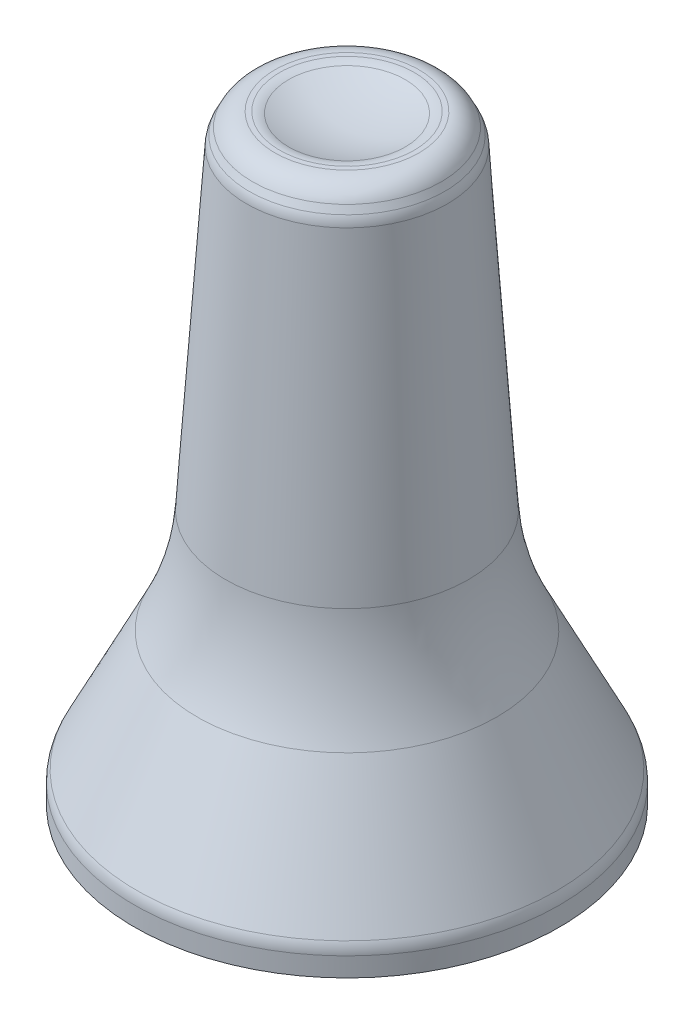
SolidWorks part; units mm, degrees
ref_plane "Front Plane" through (0, 0, 0) normal (0, 0, 1) x (1, 0, 0)
ref_plane "Top Plane" through (0, 0, 0) normal (0, 1, 0) x (1, 0, 0)
ref_plane "Right Plane" through (0, 0, 0) normal (1, 0, 0) x (0, 0, -1)
sketch "Sketch1" plane through (0, 0, 0) normal (0, 0, 1) x (1, 0, 0)
  line L0 (0, 0) -> (8.5, 0)
  line L1 (8.5, 0) -> (8.5, 1)
  line L2 (8.5, 1) -> (5, 8)
  line L3 (5, 8) -> (4, 23)
  line L4 (4, 23) -> (3.5, 24)
  line L5 (3.5, 24) -> (2.5, 24)
  line L6 (2.5, 24) -> (1.3, 23.5) construction
  line L7 (0, 23.5) -> (0, 0) construction
  line L8 (0, 0) -> (0, 23.5)
  line L9 (1.3, 23.5) -> (0, 23.5) construction
  spline S0 degree 2 poles (2.5, 24) (1.3, 23.5) (0, 23.5) knots 0 0 0 1 1 1
  dimension "D1" = 24
  dimension "D2" = 4
  dimension "D3" = 1
  dimension "D4" = 8
  dimension "D5" = 1
  dimension "D6" = 0.5
  dimension "D7" = 0.5
  dimension "D8" = 1
  dimension "D9" = 8.5
  dimension "D10" = 5
revolve "Revolve1" add sketch "Sketch1" angle 360 about L7
fillet "Fillet1" radius 11 1 edges at (-5, 8, 0)
fillet "Fillet2" radius 1 4 edges at (-2.5, 24, 0) (-3.5, 24, 0) (-4, 23, 0) (-8.5, 1, 0)
sketch "Sketch3" plane through (0, 0, 0) normal (0, 0, 1) x (1, 0, 0)
  line L0 (0, 0) -> (3.875, 0)
  line L1 (-8.5, 0) -> (8.5, 0) construction
  line L2 (3.875, 0) -> (3.875, 6.5)
  line L3 (3.875, 6.5) -> (3.05, 7.325)
  line L4 (3.05, 7.325) -> (3.05, 17.75)
  line L5 (3.05, 17.75) -> (0, 17.75)
  line L6 (0, 17.75) -> (0, 0)
  dimension "D1" = 17.75
  dimension "D2" = 3.875
  dimension "D3" = 45
  dimension "D4" = 3.05
  dimension "D5" = 6.5
revolve "Cut-Revolve1" cut sketch "Sketch3" angle 360 about L6
ref_plane "Plane1" through (0, 7.325, 0) normal (0, 1, 0) x (1, 0, 0)
sketch "Sketch4" plane through (0, 17.75, 0) normal (0, -1, 0) x (1, 0, 0)
  line L0 (-2.6557, 1.5) -> (2.6557, 1.5)
  line L5 (-999.8551, -3) -> (49000.1449, -3) construction
  arc A7 (-0.1, -3.0484) -> (0.1, -3.0484) centre (0, 0) ccw
  arc A9 (0.1, -3.0484) -> (-0.1, -3.0484) centre (0, -3.05) ccw
  arc A10 (2.6557, 1.5) -> (-2.6557, 1.5) centre (0, 0) ccw
  circle A11 centre (0, 0) radius 3.05 construction
  point P1 (-1.8297, 1.5)
  point P10 (0, 0)
  point P11 (0, 0)
  dimension "D1" = 3
  dimension "D3" = 0.2
  dimension "D2" = 4.5
extrude "Boss-Extrude1" add sketch "Sketch4" along normal up to surface (10.425 mm away) up to plane "Plane1"
chamfer "Chamfer1" distance 0.35 angle 45 1 edges at (0, 7.325, 1.5)
